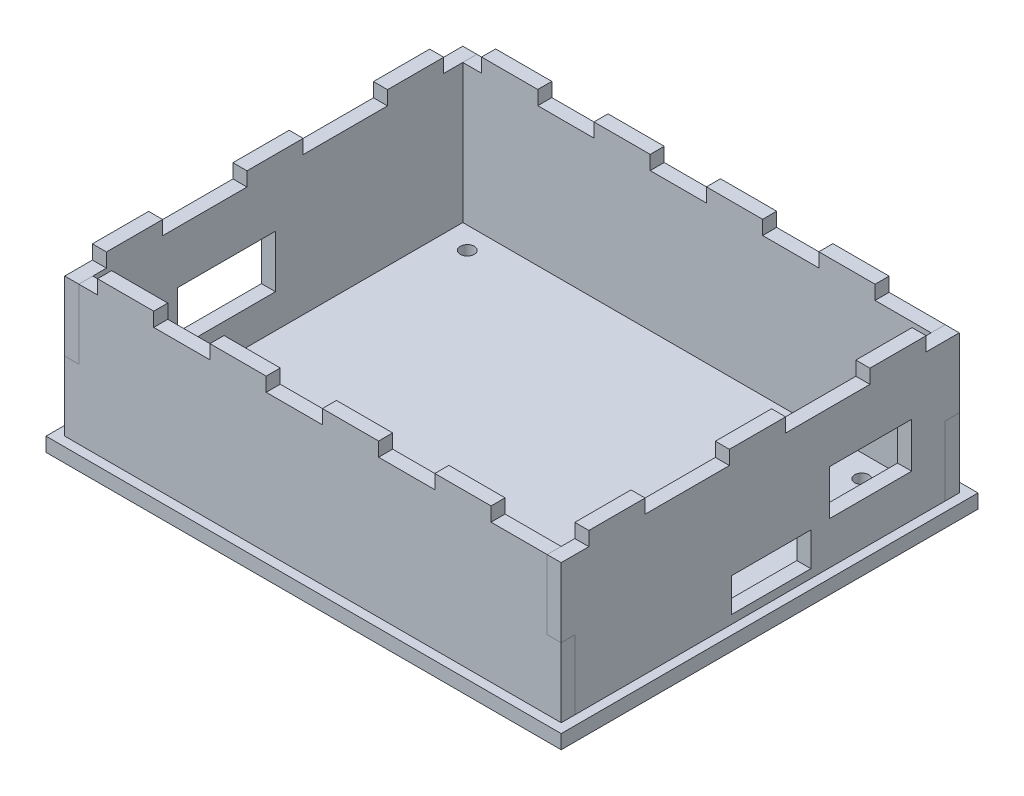
SolidWorks part; units mm, degrees
ref_plane "Front Plane" through (0, 0, 0) normal (0, 0, 1) x (1, 0, 0)
ref_plane "Top Plane" through (0, 0, 0) normal (0, 1, 0) x (1, 0, 0)
ref_plane "Right Plane" through (0, 0, 0) normal (1, 0, 0) x (0, 0, -1)
sketch "Sketch1" plane through (0, 0, 0) normal (0, 1, 0) x (1, 0, 0)
  line L0 (89.9441, -79.15) -> (89.9441, -4.1752) construction
  line L1 (-0.0307, -79.15) -> (89.9441, -79.15) construction
  line L2 (-0.0307, -4.1752) -> (-0.0307, -79.15) construction
  line L3 (89.9441, -4.1752) -> (-0.0307, -4.1752) construction
  line L13 (-0.0307, -41.6626) -> (36.6167, -41.6626) construction
  line L14 (-5.0307, -48.2445) -> (-2.0307, -48.2445)
  line L15 (-7.0307, 2.8248) -> (102.9441, 2.8248)
  line L16 (-7.0307, 2.8248) -> (-7.0307, -86.15)
  line L17 (-7.0307, -86.15) -> (102.9441, -86.15)
  line L18 (102.9441, 2.8248) -> (102.9441, -86.15)
  line L19 (-5.0307, -6.2445) -> (-2.0307, -6.2445)
  line L20 (-5.0307, -6.2445) -> (-5.0307, -18.2445)
  line L21 (-5.0307, -18.2445) -> (-2.0307, -18.2445)
  line L22 (-2.0307, -6.2445) -> (-2.0307, -18.2445)
  line L23 (-5.0307, -36.2445) -> (-5.0307, -48.2445)
  line L24 (-2.0307, -36.2445) -> (-2.0307, -48.2445)
  line L25 (-5.0307, -36.2445) -> (-2.0307, -36.2445)
  line L26 (-5.0307, -78.2445) -> (-2.0307, -78.2445)
  line L27 (-5.0307, -66.2445) -> (-5.0307, -78.2445)
  line L28 (-2.0307, -66.2445) -> (-2.0307, -78.2445)
  line L29 (-5.0307, -66.2445) -> (-2.0307, -66.2445)
  line L30 (47.9567, 2.8248) -> (47.9567, -53.2578) construction
  line L31 (100.9441, -66.2445) -> (97.9441, -66.2445)
  line L32 (97.9441, -66.2445) -> (97.9441, -78.2445)
  line L33 (100.9441, -66.2445) -> (100.9441, -78.2445)
  line L34 (100.9441, -78.2445) -> (97.9441, -78.2445)
  line L35 (100.9441, -36.2445) -> (97.9441, -36.2445)
  line L36 (97.9441, -36.2445) -> (97.9441, -48.2445)
  line L37 (100.9441, -36.2445) -> (100.9441, -48.2445)
  line L38 (97.9441, -6.2445) -> (97.9441, -18.2445)
  line L39 (100.9441, -18.2445) -> (97.9441, -18.2445)
  line L40 (100.9441, -6.2445) -> (100.9441, -18.2445)
  line L41 (100.9441, -6.2445) -> (97.9441, -6.2445)
  line L42 (100.9441, -48.2445) -> (97.9441, -48.2445)
  line L43 (1.9693, -2.1752) -> (1.9693, 0.8248)
  line L44 (1.9693, -2.1752) -> (13.9693, -2.1752)
  line L45 (13.9693, -2.1752) -> (13.9693, 0.8248)
  line L46 (1.9693, 0.8248) -> (13.9693, 0.8248)
  line L47 (25.9693, -2.1752) -> (25.9693, 0.8248)
  line L48 (25.9693, -2.1752) -> (37.9693, -2.1752)
  line L49 (25.9693, 0.8248) -> (37.9693, 0.8248)
  line L50 (37.9693, -2.1752) -> (37.9693, 0.8248)
  line L51 (49.9693, -2.1752) -> (49.9693, 0.8248)
  line L52 (49.9693, -2.1752) -> (61.9693, -2.1752)
  line L53 (49.9693, 0.8248) -> (61.9693, 0.8248)
  line L54 (61.9693, -2.1752) -> (61.9693, 0.8248)
  line L55 (73.9693, -2.1752) -> (73.9693, 0.8248)
  line L56 (73.9693, -2.1752) -> (85.9693, -2.1752)
  line L57 (73.9693, 0.8248) -> (85.9693, 0.8248)
  line L58 (85.9693, -2.1752) -> (85.9693, 0.8248)
  line L59 (47.9567, -86.15) -> (47.9567, -30.0674) construction
  line L60 (85.9693, -81.15) -> (85.9693, -84.15)
  line L61 (73.9693, -84.15) -> (85.9693, -84.15)
  line L62 (73.9693, -81.15) -> (85.9693, -81.15)
  line L63 (73.9693, -81.15) -> (73.9693, -84.15)
  line L64 (61.9693, -81.15) -> (61.9693, -84.15)
  line L65 (49.9693, -84.15) -> (61.9693, -84.15)
  line L66 (49.9693, -81.15) -> (61.9693, -81.15)
  line L67 (49.9693, -81.15) -> (49.9693, -84.15)
  line L68 (37.9693, -81.15) -> (37.9693, -84.15)
  line L69 (25.9693, -84.15) -> (37.9693, -84.15)
  line L70 (25.9693, -81.15) -> (37.9693, -81.15)
  line L71 (25.9693, -81.15) -> (25.9693, -84.15)
  line L72 (1.9693, -84.15) -> (13.9693, -84.15)
  line L73 (13.9693, -81.15) -> (13.9693, -84.15)
  line L74 (1.9693, -81.15) -> (13.9693, -81.15)
  line L75 (1.9693, -81.15) -> (1.9693, -84.15)
  circle A1 centre (2.5806, -76.4957) radius 1.5 construction
  circle A2 centre (2.8346, -6.8996) radius 1.5 construction
  arc A3 (3.2097, -4.1752) -> (2.4596, -4.1752) centre (2.8346, -6.8996) ccw construction
  circle A4 centre (87.1741, -6.9566) radius 1.5 construction
  circle A5 centre (87.9088, -6.9566) radius 1.5
  circle A6 centre (3.5806, -6.8296) radius 1.5
  circle A7 centre (3.8346, -76.4257) radius 1.5
  dimension "D5" = 5.5
  dimension "D1" = 7
  dimension "D2" = 7
  dimension "D3" = 13
  dimension "D4" = 7
  dimension "D6" = 3
  dimension "D7" = 2
  dimension "D8" = 12
  dimension "D9" = 3
  dimension "D10" = 12
  dimension "D11" = 2
  dimension "D12" = 3
  dimension "D13" = 9
  dimension "D14" = 4
extrude "Boss-Extrude7" add sketch "Sketch1" along normal blind 3
extrude "Boss-Extrude8" add sketch "Sketch1<9>" along normal blind 32.6 separate body contours L43 L46 L45 L44 | L47 L49 L50 L48 | L51 L53 L54 L52 | L55 L57 L58 L56 | L73 L72 L75 L74 | L71 L69 L68 L70 | L67 L65 L64 L66 | L63 L61 L60 L62
sketch "Sketch1<9>" plane through (0, 0, 0) normal (0, 1, 0) x (1, 0, 0) same geometry as "Sketch1"
sketch "Sketch11" plane through (0, 32.6, 0) normal (0, 1, 0) x (1, 0, 0)
  line L1 (-2.0307, -2.1752) -> (97.9441, -2.1752)
  line L2 (-2.0307, -2.1752) -> (-2.0307, 0.8248)
  line L3 (-2.0307, 0.8248) -> (97.9441, 0.8248)
  line L4 (97.9441, -2.1752) -> (97.9441, 0.8248)
  line L6 (-2.0307, -18.2445) -> (-2.0307, -6.2445) construction
  dimension "D1" = 0
extrude "Boss-Extrude10" add sketch "Sketch11" against normal blind 29.6
sketch "Sketch13" plane through (97.9441, 0, 0) normal (1, 0, 0) x (0, 0, -1)
  line L0 (0.8248, 3) -> (0.8248, 32.6) construction
  line L1 (-2.1752, 3) -> (0.8248, 3)
  line L2 (-2.1752, 3) -> (-2.1752, 17.8)
  line L3 (-2.1752, 17.8) -> (0.8248, 17.8)
  line L4 (0.8248, 3) -> (0.8248, 17.8)
  dimension "D1" = 14.8
extrude "Boss-Extrude11" add sketch "Sketch13" along normal blind 3
sketch "Sketch14" plane through (-2.0307, 0, 0) normal (-1, 0, 0) x (0, 0, 1)
  line L5 (2.1752, 3) -> (2.1752, 32.6) construction
  line L6 (-0.8248, 3) -> (2.1752, 3)
  line L7 (-0.8248, 3) -> (-0.8248, 17.8)
  line L8 (-0.8248, 17.8) -> (2.1752, 17.8)
  line L9 (2.1752, 3) -> (2.1752, 17.8)
  dimension "D1" = 14.8
extrude "Boss-Extrude12" add sketch "Sketch14" along normal blind 3
ref_plane "Plane5" through (0, 0, 41.6626) normal (0, 0, 1) x (1, 0, 0)
sketch "Sketch19" plane through (0, 32.6, 0) normal (0, 1, 0) x (1, 0, 0)
  line L0 (73.9693, 0.8248) -> (85.9693, 0.8248) construction
  line L1 (73.9693, -2.1752) -> (73.9693, 0.8248) construction
  line L2 (73.9693, -2.1752) -> (85.9693, -2.1752) construction
  line L3 (85.9693, -2.1752) -> (85.9693, 0.8248) construction
  line L4 (61.9693, -2.1752) -> (61.9693, 0.8248) construction
  line L5 (49.9693, 0.8248) -> (61.9693, 0.8248) construction
  line L6 (49.9693, -2.1752) -> (49.9693, 0.8248) construction
  line L7 (49.9693, -2.1752) -> (61.9693, -2.1752) construction
  line L8 (37.9693, -2.1752) -> (37.9693, 0.8248) construction
  line L9 (25.9693, 0.8248) -> (37.9693, 0.8248) construction
  line L10 (25.9693, -2.1752) -> (25.9693, 0.8248) construction
  line L11 (25.9693, -2.1752) -> (37.9693, -2.1752) construction
  line L12 (1.9693, -2.1752) -> (1.9693, 0.8248) construction
  line L13 (1.9693, 0.8248) -> (13.9693, 0.8248) construction
  line L14 (13.9693, -2.1752) -> (13.9693, 0.8248) construction
  line L15 (1.9693, -2.1752) -> (13.9693, -2.1752) construction
  line L16 (73.9693, 0.8248) -> (85.9693, 0.8248)
  line L17 (73.9693, -2.1752) -> (73.9693, 0.8248)
  line L18 (73.9693, -2.1752) -> (85.9693, -2.1752)
  line L19 (85.9693, -2.1752) -> (85.9693, 0.8248)
  line L20 (61.9693, -2.1752) -> (61.9693, 0.8248)
  line L21 (49.9693, 0.8248) -> (61.9693, 0.8248)
  line L22 (49.9693, -2.1752) -> (49.9693, 0.8248)
  line L23 (49.9693, -2.1752) -> (61.9693, -2.1752)
  line L24 (37.9693, -2.1752) -> (37.9693, 0.8248)
  line L25 (25.9693, 0.8248) -> (37.9693, 0.8248)
  line L26 (25.9693, -2.1752) -> (25.9693, 0.8248)
  line L27 (25.9693, -2.1752) -> (37.9693, -2.1752)
  line L28 (1.9693, -2.1752) -> (1.9693, 0.8248)
  line L29 (1.9693, 0.8248) -> (13.9693, 0.8248)
  line L30 (13.9693, -2.1752) -> (13.9693, 0.8248)
  line L31 (1.9693, -2.1752) -> (13.9693, -2.1752)
extrude "Boss-Extrude17" add sketch "Sketch19" along normal blind 3
delete or keep bodies "Body-Delete/Keep 1" type delete bodies bodies 115
delete or keep bodies "Body-Delete/Keep 2" type delete bodies bodies 116
delete or keep bodies "Body-Delete/Keep 3" type delete bodies bodies 117
delete or keep bodies "Body-Delete/Keep 4" type delete bodies bodies 118
extrude "Boss-Extrude18" add sketch "Sketch1<10>" along normal blind 32.6 separate body contours L42 L37 L35 L36 | L34 L33 L31 L32 | L39 L38 L41 L40 region at (99.4441, 0, 72.2445) region at (99.4441, 0, 42.2445)
sketch "Sketch1<10>" plane through (0, 0, 0) normal (0, 1, 0) x (1, 0, 0) same geometry as "Sketch1"
sketch "Sketch23" plane through (0, 3, 0) normal (0, 1, 0) x (1, 0, 0)
  line L0 (100.9441, -6.2445) -> (100.9441, -18.2445) construction
  line L1 (97.9441, -2.1752) -> (100.9441, -2.1752)
  line L2 (97.9441, -2.1752) -> (97.9441, -81.15)
  line L3 (97.9441, -81.15) -> (100.9441, -81.15)
  line L4 (100.9441, -2.1752) -> (100.9441, -81.15)
  line L5 (73.9693, -81.15) -> (85.9693, -81.15) construction
extrude "Boss-Extrude22" add sketch "Sketch23" along normal blind 29.6
sketch "Sketch24" plane through (0, 0, 2.1752) normal (0, 0, -1) x (-1, 0, 0)
  line L0 (-97.9441, 32.6) -> (-97.9441, 3) construction
  line L1 (-100.9441, 32.6) -> (-97.9441, 32.6)
  line L2 (-100.9441, 32.6) -> (-100.9441, 17.8)
  line L3 (-100.9441, 17.8) -> (-97.9441, 17.8)
  line L4 (-97.9441, 32.6) -> (-97.9441, 17.8)
extrude "Boss-Extrude23" add sketch "Sketch24" along normal blind 3
sketch "Sketch25" plane through (0, 0, 81.15) normal (0, 0, 1) x (1, 0, 0)
  line L0 (100.9441, 32.6) -> (100.9441, 3) construction
  line L1 (97.9441, 32.6) -> (100.9441, 32.6)
  line L2 (97.9441, 32.6) -> (97.9441, 17.8)
  line L3 (97.9441, 17.8) -> (100.9441, 17.8)
  line L4 (100.9441, 32.6) -> (100.9441, 17.8)
extrude "Boss-Extrude24" add sketch "Sketch25" along normal blind 3
sketch "Sketch26" plane through (0, 32.6, 0) normal (0, 1, 0) x (1, 0, 0)
  line L0 (100.9441, -78.2445) -> (97.9441, -78.2445) construction
  line L1 (97.9441, -66.2445) -> (97.9441, -78.2445) construction
  line L2 (100.9441, -66.2445) -> (100.9441, -78.2445) construction
  line L3 (100.9441, -66.2445) -> (97.9441, -66.2445) construction
  line L4 (100.9441, -48.2445) -> (97.9441, -48.2445) construction
  line L5 (97.9441, -36.2445) -> (97.9441, -48.2445) construction
  line L6 (100.9441, -36.2445) -> (100.9441, -48.2445) construction
  line L7 (100.9441, -36.2445) -> (97.9441, -36.2445) construction
  line L8 (100.9441, -6.2445) -> (97.9441, -6.2445) construction
  line L9 (100.9441, -6.2445) -> (100.9441, -18.2445) construction
  line L10 (100.9441, -18.2445) -> (97.9441, -18.2445) construction
  line L11 (97.9441, -6.2445) -> (97.9441, -18.2445) construction
  line L12 (100.9441, -78.2445) -> (97.9441, -78.2445)
  line L13 (97.9441, -66.2445) -> (97.9441, -78.2445)
  line L14 (100.9441, -66.2445) -> (100.9441, -78.2445)
  line L15 (100.9441, -66.2445) -> (97.9441, -66.2445)
  line L16 (100.9441, -48.2445) -> (97.9441, -48.2445)
  line L17 (97.9441, -36.2445) -> (97.9441, -48.2445)
  line L18 (100.9441, -36.2445) -> (100.9441, -48.2445)
  line L19 (100.9441, -36.2445) -> (97.9441, -36.2445)
  line L20 (100.9441, -6.2445) -> (97.9441, -6.2445)
  line L21 (100.9441, -6.2445) -> (100.9441, -18.2445)
  line L22 (100.9441, -18.2445) -> (97.9441, -18.2445)
  line L23 (97.9441, -6.2445) -> (97.9441, -18.2445)
extrude "Boss-Extrude25" add sketch "Sketch26" along normal blind 3
ref_plane "Plane6" through (47.9567, 0, 0) normal (-1, 0, 0) x (0, 0, 1)
mirror "Mirror4" about plane through (47.9567, 0, 0) normal (-1, 0, 0) of bodies 137
mirror "Mirror5" about plane through (0, 0, 41.6626) normal (0, 0, 1) of bodies 130
sketch "Sketch28" plane through (100.9441, 0, 0) normal (1, 0, 0) x (0, 0, -1)
  line L32 (-36.2445, 3) -> (-18.2445, 3)
  line L33 (-18.2445, 3) -> (-18.2445, 0)
  line L34 (-18.2445, 0) -> (-6.2445, 0)
  line L35 (-6.2445, 0) -> (-6.2445, 3)
  line L36 (-6.2445, 3) -> (-2.1752, 3)
  line L37 (-2.1752, 3) -> (-2.1752, 17.8)
  line L38 (-2.1752, 17.8) -> (0.8248, 17.8)
  line L39 (0.8248, 17.8) -> (0.8248, 32.6)
  line L40 (0.8248, 32.6) -> (-6.2445, 32.6)
  line L41 (-6.2445, 32.6) -> (-6.2445, 35.6)
  line L42 (-6.2445, 35.6) -> (-18.2445, 35.6)
  line L43 (-18.2445, 35.6) -> (-18.2445, 32.6)
  line L44 (-18.2445, 32.6) -> (-36.2445, 32.6)
  line L45 (-36.2445, 32.6) -> (-36.2445, 35.6)
  line L46 (-36.2445, 35.6) -> (-48.2445, 35.6)
  line L47 (-48.2445, 35.6) -> (-48.2445, 32.6)
  line L48 (-48.2445, 32.6) -> (-66.2445, 32.6)
  line L49 (-66.2445, 32.6) -> (-66.2445, 35.6)
  line L50 (-66.2445, 35.6) -> (-78.2445, 35.6)
  line L51 (-78.2445, 35.6) -> (-78.2445, 32.6)
  line L52 (-78.2445, 32.6) -> (-84.15, 32.6)
  line L53 (-84.15, 32.6) -> (-84.15, 17.8)
  line L54 (-84.15, 17.8) -> (-81.15, 17.8)
  line L55 (-81.15, 17.8) -> (-81.15, 3)
  line L56 (-81.15, 3) -> (-78.2445, 3)
  line L57 (-78.2445, 3) -> (-78.2445, 0)
  line L58 (-78.2445, 0) -> (-66.2445, 0)
  line L59 (-66.2445, 0) -> (-66.2445, 3)
  line L60 (-66.2445, 3) -> (-48.2445, 3)
  line L61 (-48.2445, 3) -> (-48.2445, 0)
  line L62 (-48.2445, 0) -> (-36.2445, 0)
  line L63 (-36.2445, 0) -> (-36.2445, 3)
  line L64 (-36.2445, 3) -> (-18.2445, 3)
  line L65 (-18.2445, 3) -> (-18.2445, 0)
  line L66 (-18.2445, 0) -> (-6.2445, 0)
  line L67 (-6.2445, 0) -> (-6.2445, 3)
  line L68 (-6.2445, 3) -> (-2.1752, 3)
  line L69 (-2.1752, 3) -> (-2.1752, 17.8)
  line L70 (-2.1752, 17.8) -> (0.8248, 17.8)
  line L71 (0.8248, 17.8) -> (0.8248, 32.6)
  line L72 (0.8248, 32.6) -> (-6.2445, 32.6)
  line L73 (-6.2445, 32.6) -> (-6.2445, 35.6)
  line L74 (-6.2445, 35.6) -> (-18.2445, 35.6)
  line L75 (-18.2445, 35.6) -> (-18.2445, 32.6)
  line L76 (-18.2445, 32.6) -> (-36.2445, 32.6)
  line L77 (-36.2445, 32.6) -> (-36.2445, 35.6)
  line L78 (-36.2445, 35.6) -> (-48.2445, 35.6)
  line L79 (-48.2445, 35.6) -> (-48.2445, 32.6)
  line L80 (-48.2445, 32.6) -> (-66.2445, 32.6)
  line L81 (-66.2445, 32.6) -> (-66.2445, 35.6)
  line L82 (-66.2445, 35.6) -> (-78.2445, 35.6)
  line L83 (-78.2445, 35.6) -> (-78.2445, 32.6)
  line L84 (-78.2445, 32.6) -> (-84.15, 32.6)
  line L85 (-84.15, 32.6) -> (-84.15, 17.8)
  line L86 (-84.15, 17.8) -> (-81.15, 17.8)
  line L87 (-81.15, 17.8) -> (-81.15, 3)
  line L88 (-81.15, 3) -> (-78.2445, 3)
  line L89 (-78.2445, 3) -> (-78.2445, 0)
  line L90 (-78.2445, 0) -> (-66.2445, 0)
  line L91 (-66.2445, 0) -> (-66.2445, 3)
  line L92 (-66.2445, 3) -> (-48.2445, 3)
  line L93 (-48.2445, 3) -> (-48.2445, 0)
  line L94 (-48.2445, 0) -> (-36.2445, 0)
  line L95 (-36.2445, 0) -> (-36.2445, 3)
  dimension "D1" = 0
sketch "Sketch29" plane through (100.9441, 0, 0) normal (1, 0, 0) x (0, 0, -1)
  line L0 (-46.2466, 11.0297) -> (-46.2466, 5.8297) construction
  line L1 (-47.7466, 4.8297) -> (-30.8466, 4.8297)
  line L2 (-47.7466, 4.8297) -> (-47.7466, 12)
  line L3 (-47.7466, 12) -> (-30.8466, 12)
  line L4 (-30.8466, 4.8297) -> (-30.8466, 12)
  line L5 (-4.1752, 11) -> (-79.15, 11) construction
  line L6 (-46.2466, 5.8297) -> (-32.3466, 5.8297) construction
  line L7 (-32.3466, 5.8297) -> (-32.3466, 11.0297) construction
  line L8 (-25.8394, 12.6001) -> (-25.8394, 19.9001) construction
  line L9 (-26.8394, 12.1001) -> (-9.3394, 12.1001)
  line L10 (-26.8394, 12.1001) -> (-26.8394, 21.7001)
  line L11 (-26.8394, 21.7001) -> (-9.3394, 21.7001)
  line L12 (-9.3394, 12.1001) -> (-9.3394, 21.7001)
  line L13 (-25.0394, 20.7001) -> (-11.1394, 20.7001) construction
  line L14 (-10.3394, 19.9001) -> (-10.3394, 12.6001) construction
  line L15 (-79.15, 12.6001) -> (-4.1752, 12.6001) construction
  dimension "D1" = 1.5
  dimension "D2" = 1
  dimension "D3" = 1
  dimension "D4" = 1.5
  dimension "D5" = 1
  dimension "D6" = 1
  dimension "D7" = 1
  dimension "D8" = 0.5
extrude "Cut-Extrude4" cut sketch "Sketch29" against normal blind 10 contours L4 L3 L2 L1 | L11 L12 L9 L10
sketch "Sketch30" plane through (-5.0307, 0, 0) normal (-1, 0, 0) x (0, 0, 1)
  line L0 (57.1053, 16.3999) -> (57.1053, 15.2) construction
  line L1 (63.1053, 21.3998) -> (42.1659, 21.3998)
  line L2 (63.1053, 21.3998) -> (63.1053, 10.2)
  line L3 (63.1053, 10.2) -> (42.1659, 10.2)
  line L4 (42.1659, 21.3998) -> (42.1659, 10.2)
  line L5 (48.1659, 15.2) -> (48.1659, 16.3999) construction
  line L6 (49.1659, 17.3998) -> (56.1053, 17.3998) construction
  line L7 (62.1356, 14.2) -> (43.1356, 14.2) construction
  dimension "D1" = 6
  dimension "D2" = 6
  dimension "D3" = 4
  dimension "D4" = 4
extrude "Cut-Extrude5" cut sketch "Sketch30" against normal blind 10
